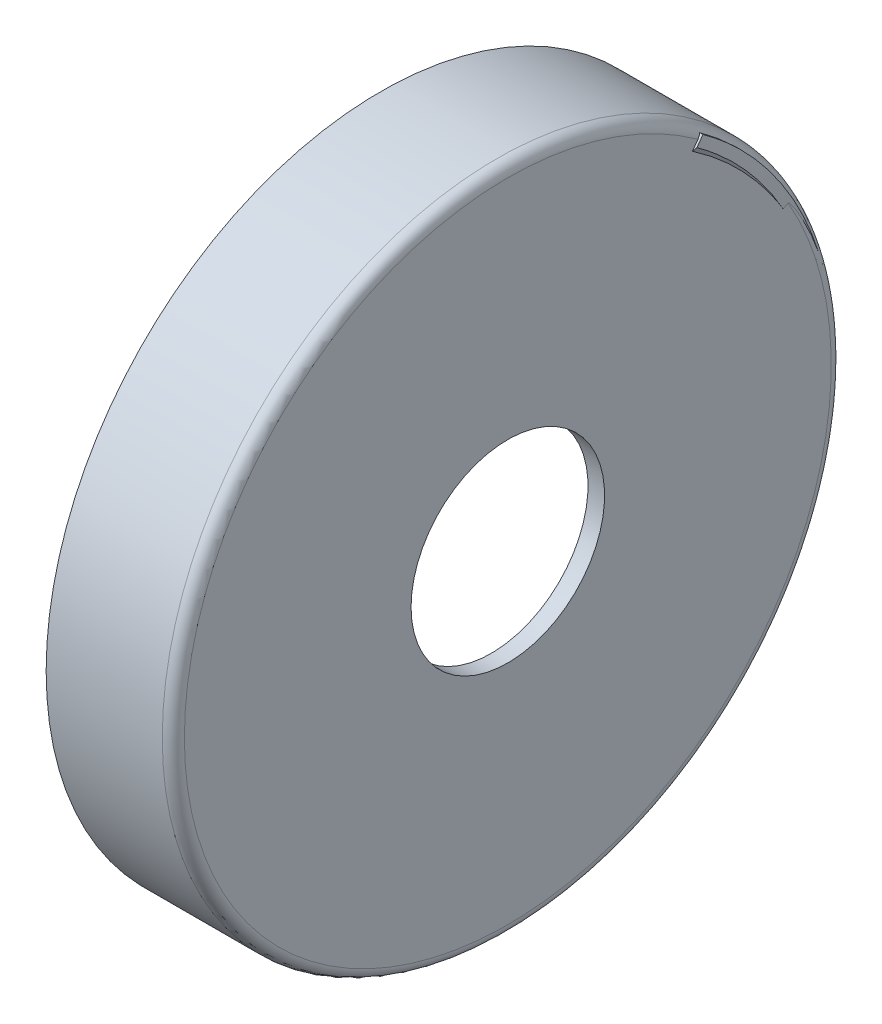
SolidWorks part; units mm, degrees
note: '?' marks a value the reader was unsure of.
ref_plane "Front" through (0, 0, 0) normal (0, 0, 1) x (1, 0, 0)
ref_plane "Top" through (0, 0, 0) normal (0, 1, 0) x (1, 0, 0)
ref_plane "Side" through (0, 0, 0) normal (1, 0, 0) x (0, 0, -1)
ref_axis "X_Axis" through (-20.1896, 0, 0) along (1, 0, 0)?
ref_axis "Y_Axis" through (0, -14.8261, 0) along (0, 1, 0)?
ref_axis "Z_Axis" through (0, 0, -19.842) along (0, 0, 1)?
sketch "Sketch1" plane through (0, 0, 0) normal (0, 0, 1) x (1, 0, 0)
  line L0 (0, 60.5) -> (21, 60.5)
  line L1 (23, 58.5) -> (23, 17.5)
  line L3 (20, 17.5) -> (20, 55.5)
  line L4 (18, 57.5) -> (0, 57.5)
  line L5 (0, 57.5) -> (0, 60.5)
  line L6 (0, 0) -> (57.066, 0) construction
  line L12 (23, 17.5) -> (20, 17.5)
  arc A1 (20, 55.5) -> (18, 57.5) centre (18, 55.5) ccw
  arc A2 (21, 60.5) -> (23, 58.5) centre (21, 58.5) cw
  point P20 (20, 57.5)
  dimension "D9" = 2
  dimension "D1" = 115
  dimension "D2" = 121
  dimension "D3" = 17.5
  dimension "D6" = 3
  dimension "D7" = 20
revolve "Revolve1" add sketch "Sketch1" angle 360 about L6
sketch "Sketch2" plane through (0, 0, 0) normal (-1, 0, 0) x (0, 0, 1)
  circle A0 centre (0, 0) radius 57.5 construction
  circle A1 centre (0, 0) radius 57.5
curve "Helix/Spiral1" pitch 6 height 26.4 turns 4.4
sketch "Sketch3" plane through (0, 0, 0) normal (0, 0, 1) x (1, 0, 0)
  line L0 (0, 57.5) -> (-2.1494, 53.7771)
  line L1 (-3.6506, 53.7771) -> (-5.8, 57.5)
  line L2 (-5.8, 57.5) -> (-5.8, 59.3656)
  line L3 (-5.8, 59.3656) -> (0, 59.3656)
  line L4 (0, 60.5) -> (0, -60.5) construction
  line L5 (0, 59.3656) -> (0, 57.5)
  line L6 (-2.9, 52.4771) -> (-2.9, 59.3656) construction
  line L7 (-3.6506, 53.7771) -> (-2.1494, 53.7771)
  point P12 (-2.9, 53.7771)
  dimension "D1" = 60
  dimension "D2" = 5.8
  dimension "D3" = 1.3
  dimension "D4" = 3.7229
sweep "Sweep1" add profiles "Sketch3" path "Helix/Spiral1"
sketch "Sketch4" plane through (0, 0, 0) normal (-1, 0, 0) x (0, 0, 1)
  circle A0 centre (0, 0) radius 60.5
  circle A1 centre (0, 0) radius 60.5 construction
extrude "Cut-Extrude1" cut sketch "Sketch4" along normal through all
